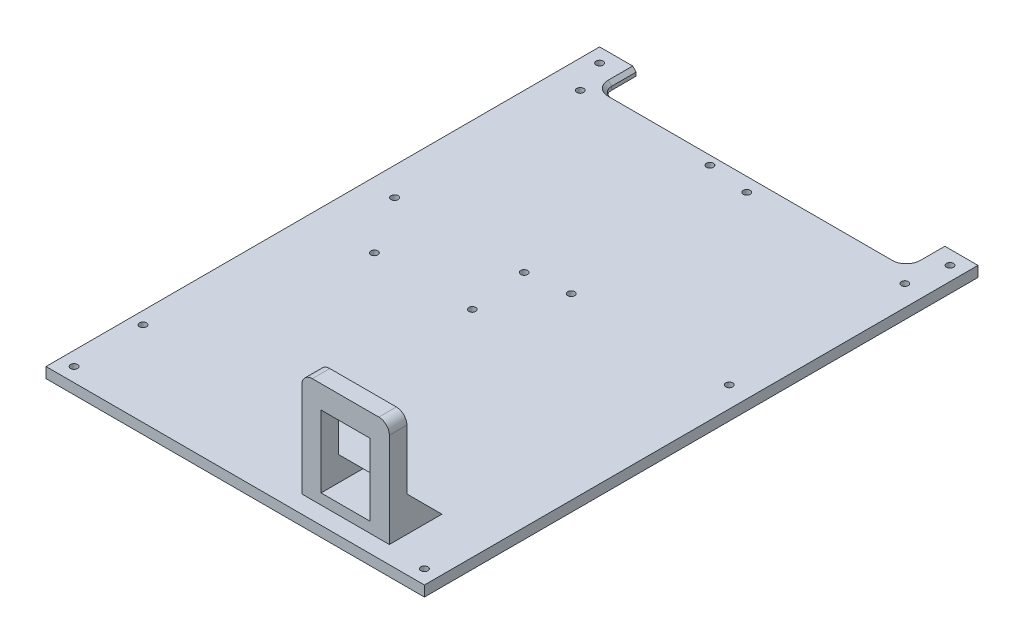
SolidWorks part; units mm, degrees
ref_plane "Plano frontal" through (0, 0, 0) normal (0, 0, 1) x (1, 0, 0)
ref_plane "Plano superior" through (0, 0, 0) normal (0, 1, 0) x (1, 0, 0)
ref_plane "Plano direito" through (0, 0, 0) normal (1, 0, 0) x (0, 0, -1)
sketch "Esboço1" plane through (0, 0, 0) normal (0, 1, 0) x (1, 0, 0)
  line L1 (55, -80) -> (-55, -80)
  line L2 (55, -80) -> (55, 80)
  line L3 (55, 80) -> (-55, 80)
  line L4 (-55, -80) -> (-55, 80)
  line L5 (55, -80) -> (-55, 80) construction
  line L6 (55, 80) -> (-55, -80) construction
  point P0 (0, 0)
  dimension "D1" = 160
  dimension "D2" = 110
extrude "Ressalto-extrusão1" add sketch "Esboço1" along normal blind 3
sketch "Esboço3" plane through (0, 3, 0) normal (0, 1, 0) x (1, 0, 0)
  line L8 (-54, 79) -> (-54, -79)
  line L9 (-54, -79) -> (54, -79)
  line L10 (54, -79) -> (54, 79)
  line L11 (54, 79) -> (-54, 79)
  line L12 (-54, 79) -> (-54, -79)
  line L13 (-54, -79) -> (54, -79)
  line L14 (54, -79) -> (54, 79)
  line L15 (54, 79) -> (-54, 79)
  line L16 (-55, 80) -> (-55, -80)
  line L17 (-55, -80) -> (55, -80)
  line L18 (55, -80) -> (55, 80)
  line L19 (55, 80) -> (-55, 80)
  line L20 (-55, 80) -> (-55, -80)
  line L21 (-55, -80) -> (55, -80)
  line L22 (55, -80) -> (55, 80)
  line L23 (55, 80) -> (-55, 80)
  line L24 (-50, 75) -> (-50, -75)
  line L25 (-50, -75) -> (50, -75)
  line L26 (50, -75) -> (50, 75)
  line L27 (50, 75) -> (-50, 75)
  line L28 (-50, 75) -> (-50, -75) construction
  line L29 (-50, -75) -> (50, -75) construction
  line L30 (50, -75) -> (50, 75) construction
  line L31 (50, 75) -> (-50, 75) construction
  circle A0 centre (-50, -75) radius 1
  circle A1 centre (-50, 75) radius 1
  circle A2 centre (50, -75) radius 1
  circle A3 centre (50, 75) radius 1
  line M9 (-55, 80) -> (-55, -80)
  line M10 (-55, -80) -> (55, -80)
  line M11 (55, -80) -> (55, 80)
  line M12 (55, 80) -> (-55, 80)
  dimension "D4" = 2
  dimension "D1" = 1
  dimension "D2" = 0
  dimension "D3" = 5
extrude "Corte-extrusão1" cut sketch "Esboço3" against normal through all contours L15 L14 L13 L12 M12 M9 M10 M11 | A0 | A2 | A3 | A1
sketch "Esboço5" plane through (0, 3, 0) normal (0, 1, 0) x (1, 0, 0)
  line L0 (54, 79) -> (-54, 79) construction
  line L1 (54, -79) -> (54, 79) construction
  line L2 (43.5495, 79) -> (43.5495, 69)
  line L3 (43.5495, 69) -> (-43.5495, 69)
  line L4 (-43.5495, 79) -> (-43.5495, 69)
  line L5 (0, 79) -> (-43.5495, 69) construction
  line L6 (43.5495, 69) -> (0, 79) construction
  line L7 (-43.5495, 79) -> (43.5495, 79)
  point P0 (0, 79)
  point P2 (43.5495, 74)
  dimension "D1" = 10.4505
  dimension "D2" = 10
extrude "Corte-extrusão2" cut sketch "Esboço5" against normal through all
sketch "Esboço6" plane through (0, 3, 0) normal (0, 1, 0) x (1, 0, 0)
  line L1 (39, -74) -> (14, -74)
  line L2 (39, -74) -> (39, -69)
  line L3 (39, -69) -> (14, -69)
  line L4 (14, -74) -> (14, -69)
  line L5 (54, -79) -> (54, 79) construction
  line L6 (-54, -79) -> (54, -79) construction
  dimension "D1" = 5
  dimension "D2" = 25
  dimension "D3" = 15
  dimension "D4" = 5
extrude "Ressalto-extrusão2" add sketch "Esboço6" along normal blind 30
sketch "Esboço7" plane through (0, 0, 79) normal (0, 0, 1) x (1, 0, 0)
  line L0 (-54, 3) -> (54, 3) construction
  line L1 (33.5, 26.5) -> (19.5, 26.5)
  line L2 (33.5, 26.5) -> (33.5, 6)
  line L3 (33.5, 6) -> (19.5, 6)
  line L4 (19.5, 26.5) -> (19.5, 6)
  line L5 (26.5, 26.5) -> (14, 26.5) construction
  line L6 (26.5, 26.5) -> (39, 26.5) construction
  line L7 (39, 33) -> (39, 3) construction
  line L8 (14, 33) -> (14, 3) construction
  dimension "D1" = 14
  dimension "D2" = 20.5
  dimension "D3" = 3
extrude "Corte-extrusão3" cut sketch "Esboço7" against normal through all
sketch "Esboço8" plane through (0, 3, 0) normal (0, 1, 0) x (1, 0, 0)
  circle A0 centre (-9, 65.4823) radius 1.5 construction
  circle A1 centre (-46, 65.4823) radius 1.5 construction
  circle A2 centre (-35.22, -4.0577) radius 1.5875 construction
  circle A3 centre (48.05, 64.05) radius 1.75 construction
  circle A4 centre (2.95, 64.05) radius 1.75 construction
  circle A5 centre (-46, 12.4823) radius 1.5 construction
  circle A6 centre (-9, 12.4823) radius 1.5 construction
  circle A7 centre (48.05, 13.95) radius 1.75 construction
  circle A8 centre (2.95, 13.95) radius 1.75 construction
  circle A9 centre (-7.28, -4.0577) radius 1.5875 construction
  circle A10 centre (-50.46, -54.8577) radius 1.5875 construction
  circle A11 centre (-2.2, -56.1277) radius 1.5875 construction
  circle A12 centre (-9, 65.4823) radius 1.5 construction
  circle A13 centre (-46, 65.4823) radius 1.5 construction
  circle A14 centre (-35.22, -4.0577) radius 1.5875 construction
  circle A15 centre (48.05, 64.05) radius 1.75 construction
  circle A16 centre (2.95, 64.05) radius 1.75 construction
  circle A17 centre (-46, 12.4823) radius 1.5 construction
  circle A18 centre (-9, 12.4823) radius 1.5 construction
  circle A19 centre (48.05, 13.95) radius 1.75 construction
  circle A20 centre (2.95, 13.95) radius 1.75 construction
  circle A21 centre (-7.28, -4.0577) radius 1.5875 construction
  circle A22 centre (-50.46, -54.8577) radius 1.5875 construction
  circle A23 centre (-2.2, -56.1277) radius 1.5875 construction
  circle A24 centre (-50.46, -54.8577) radius 1
  circle A25 centre (-2.2, -56.1277) radius 1
  circle A26 centre (-7.28, -4.0577) radius 1
  circle A27 centre (-35.22, -4.0577) radius 1
  circle A28 centre (48.05, 13.95) radius 1
  circle A29 centre (2.95, 13.95) radius 1
  circle A30 centre (-9, 12.4823) radius 1
  circle A31 centre (-46, 12.4823) radius 1
  circle A32 centre (48.05, 64.05) radius 1
  circle A33 centre (2.95, 64.05) radius 1
  circle A34 centre (-9, 65.4823) radius 1
  circle A35 centre (-46, 65.4823) radius 1
  dimension "D1" = 2
extrude "Corte-extrusão4" cut sketch "Esboço8" against normal through all
chamfer "Chanfro1" distance 10 angle 45 1 edges at (26.5, 3, 69)
fillet "Filete1" radius 3 2 edges at (14, 33, 71.5) (39, 33, 71.5)
fillet "Filete2" radius 3 2 edges at (43.5495, 1.5, -69) (-43.5495, 1.5, -69)
chamfer "Chanfro2" distance 1 angle 45 10 edges at (-43.5495, 3, -75.5) (43.5495, 3, -75.5) (-42.6708, 3, -69.8787) (42.6708, 3, -69.8787) (0, 3, -69) (-43.5495, 0, -75.5) (43.5495, 0, -75.5) (-42.6708, 0, -69.8787) (42.6708, 0, -69.8787) (0, 0, -69)
